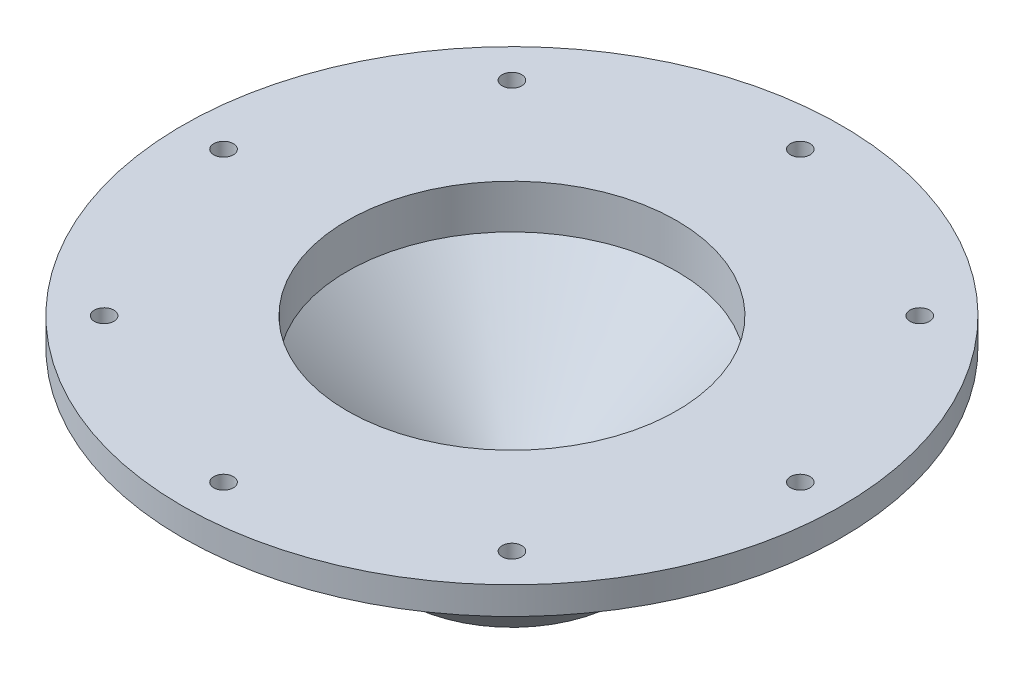
SolidWorks part; units mm, degrees
ref_plane "Front Plane" through (0, 0, 0) normal (0, 0, 1) x (1, 0, 0)
ref_plane "Top Plane" through (0, 0, 0) normal (0, 1, 0) x (1, 0, 0)
ref_plane "Right Plane" through (0, 0, 0) normal (1, 0, 0) x (0, 0, -1)
sketch "Sketch1" plane through (0, 0, 0) normal (0, 1, 0) x (1, 0, 0)
  circle A0 centre (0, 0) radius 38.1
  dimension "D1" = 76.2
extrude "Boss-Extrude1" add sketch "Sketch1" along normal blind 3.175
hole_wizard "Tap Drill for #4-40 Tap1" positions "Sketch3" profile "Sketch4" hole size "#4-40" standard "ANSI Inch" end condition through all
sketch "Sketch3" plane through (0, 0, 0) normal (0, -1, 0) x (-1, 0, 0)
  point P0 (0, -33.3375)
  dimension "D1" = 33.3375
sketch "Sketch4" plane through (0, 0, 33.3375) normal (1, 0, 0) x (0, 0, -1)
  line L0 (0, 0) -> (0, 3.175)
  line L1 (0, 3.175) -> (1.1303, 3.175)
  line L2 (1.1303, 3.175) -> (1.1303, 0)
  line L5 (1.1303, 0) -> (0, 0)
  line L11 (0, -6.35) -> (0, 107.95) construction
  dimension "Thru Hole Dia." = 2.2606
  dimension "Thru Hole Depth" = 3.175
pattern_circular "CirPattern1" count 8 over 360 about axis through (0, 0, 0) along (0, 1, 0) of "Tap Drill for #4-40 Tap1"
sketch "Sketch5" plane through (0, 0, 0) normal (0, -1, 0) x (1, 0, 0)
  circle A0 centre (0, 0) radius 25.4
  dimension "D1" = 50.8
extrude "Boss-Extrude2" add sketch "Sketch5" along normal blind 19.05
sketch "Sketch6" plane through (0, -19.05, 0) normal (0, -1, 0) x (1, 0, 0)
  circle A0 centre (0, 0) radius 4.7625
  dimension "D1" = 9.525
extrude "Cut-Extrude1" cut sketch "Sketch6" against normal through all both and the other way through all
sketch "Sketch7" plane through (0, 3.175, 0) normal (0, 1, 0) x (1, 0, 0)
  circle A0 centre (0, 0) radius 19.05
  dimension "D1" = 38.1
extrude "Cut-Extrude2" cut sketch "Sketch7" against normal blind 5.08
sketch "Sketch8" plane through (0, -1.905, 0) normal (0, 1, 0) x (1, 0, 0)
  circle A0 centre (0, 0) radius 19.05
  circle A1 centre (0, 0) radius 19.05 construction
  dimension "D1" = 0
ref_plane "Plane1" through (0, -15.875, 0) normal (0, -1, 0) x (-1, 0, 0)
sketch "Sketch9" plane through (0, -15.875, 0) normal (0, -1, 0) x (-1, 0, 0)
  circle A0 centre (0, 0) radius 4.7625
  circle A1 centre (0, 0) radius 4.7625 construction
  dimension "D1" = 0
loft "Cut-Loft1" cut profiles "Sketch8", "Sketch9" connector at (0, -1.905, 19.05) connector at (-1.301, -15.875, 4.5814)
chamfer "Chamfer1" distance 12.7 angle 45 1 edges at (0, -19.05, -25.4)
fillet "Fillet1" radius 1.27 1 edges at (0, 0, 25.4)
